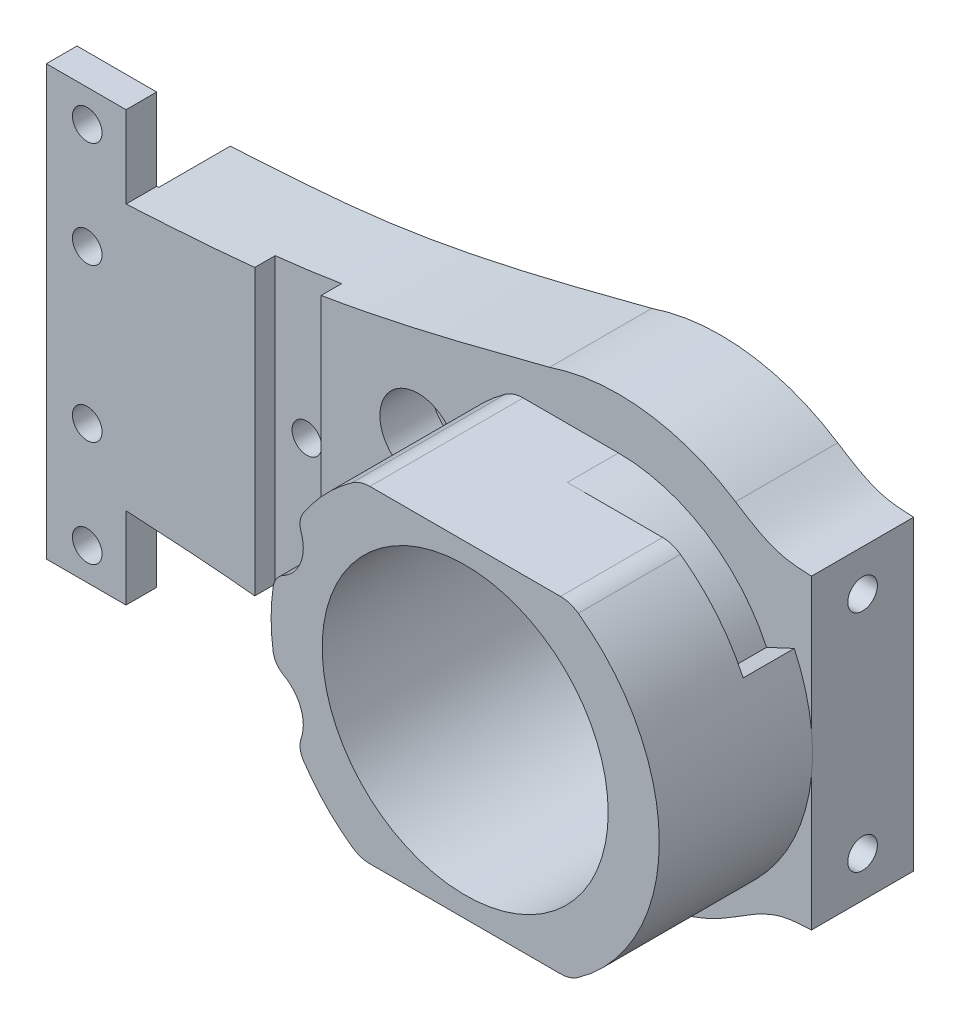
SolidWorks part; units mm, degrees
ref_plane "Front Plane" through (0, 0, 0) normal (0, 0, 1) x (1, 0, 0)
ref_plane "Top Plane" through (0, 0, 0) normal (0, 1, 0) x (1, 0, 0)
ref_plane "Right Plane" through (0, 0, 0) normal (1, 0, 0) x (0, 0, -1)
sketch "Sketch1" plane through (0, 0, 0) normal (0, 0, 1) x (1, 0, 0)
  line L0 (-30, 21) -> (-22.2, 21)
  line L1 (44.9, 15) -> (44.9, -15)
  line L2 (-22.2, 21) -> (-22.2, 13)
  line L3 (-30, -21) -> (-30, 21)
  line L4 (-30, 0) -> (0, 0) construction
  line L5 (0, 0) -> (44.9, 0) construction
  line L6 (-30, -21) -> (-22.2, -21)
  line L7 (-22.2, -21) -> (-22.2, -13)
  circle A0 centre (26, 0) radius 14
  arc A1 (19.2579, -19.8883) -> (37.4703, -17.5907) centre (26, 0) ccw
  arc A2 (37.4703, 17.5907) -> (19.2579, 19.8883) centre (26, 0) ccw
  spline S0 degree 3 poles (-22.2, 13) (-17.0873, 13.2934) (-3.0476, 14.0991) (10.5879, 17.6381) (19.2579, 19.8883) knots 0 0 0 0 0.364161 1 1 1 1
  spline S1 degree 3 poles (-22.2, -13) (-17.0873, -13.2934) (-3.0476, -14.0991) (10.5879, -17.6381) (19.2579, -19.8883) knots 0 0 0 0 0.364161 1 1 1 1
  spline S2 degree 3 poles (44.9, 15) (43.9598, 15.0415) (41.2679, 15.1604) (38.9674, 16.6326) (37.4703, 17.5907) knots 0 0 0 0 0.349252 1 1 1 1
  spline S3 degree 3 poles (44.9, -15) (43.9598, -15.0415) (41.2679, -15.1604) (38.9674, -16.6326) (37.4703, -17.5907) knots 0 0 0 0 0.349252 1 1 1 1
  dimension "D4" = 28
  dimension "D5" = 42
  dimension "D1" = 74.9
  dimension "D2" = 42
  dimension "D3" = 30
  dimension "D6" = 56
  dimension "D7" = 30
  dimension "D8" = 7.8
  dimension "D9" = 8
extrude "Extrude1" add sketch "Sketch1" along normal blind 10
sketch "Sketch3" plane through (0, 0, 10) normal (0, 0, 1) x (1, 0, 0)
  circle A0 centre (26, 0) radius 19
  circle A1 centre (26, 0) radius 14
  dimension "D1" = 38
extrude "Extrude2" add sketch "Sketch3" along normal blind 15
sketch "Sketch4" plane through (0, 0, 0) normal (0, 0, -1) x (-1, 0, 0)
  line L0 (30, 21) -> (30, -21) construction
  line L1 (30, 23.4126) -> (22, 23.4126)
  line L2 (30, 23.4126) -> (30, -25.9867)
  line L3 (30, -25.9867) -> (22, -25.9867)
  line L4 (22, 23.4126) -> (22, -25.9867)
  dimension "D1" = 8
extrude "Extrude3" cut sketch "Sketch4" against normal blind 7
hole_wizard "CBORE for M3 Pan Head Machine Screw1" positions "3DSketch1" profile "Sketch5" counterbore size "M3" standard "Ansi Metric" end condition through all
sketch3d "3DSketch1"
  line L0 (6.4, 7.5, 10) -> (6.4, -7.5, 10) construction
  line L3 (6.4, 0, 10) -> (0, 0, 10) construction
  line L4 (-30, 21, 10) -> (-30, -21, 10) construction
  point P0 (6.4, 7.5, 10)
  point P2 (6.4, -7.5, 10)
  dimension "D1" = 7.5
  dimension "D2" = 7.5
  dimension "D3" = 36.4
sketch "Sketch5" plane through (6.4, 7.5, 10) normal (1, 0, 0) x (0, -1, 0)
  line L0 (0, 0) -> (0, 10)
  line L1 (0, 10) -> (1.8, 10)
  line L3 (1.8, 10) -> (1.8, 5)
  line L4 (1.8, 5) -> (3.75, 5)
  line L5 (3.75, 5) -> (3.75, 0)
  line L7 (3.75, 0) -> (0, 0)
  line L11 (0, -6.35) -> (0, 107.95) construction
  dimension "Thru Hole Dia." = 3.6
  dimension "Thru Hole Depth" = 10
  dimension "C'Bore Dia." = 7.5
  dimension "C'Bore Depth" = 5
sketch "Sketch6" plane through (0, 0, 10) normal (0, 0, 1) x (1, 0, 0)
  circle A0 centre (6.4, 7.5) radius 3.75
  circle A1 centre (6.4, -7.5) radius 3.75
  circle A2 centre (6.4, 7.5) radius 3.75 construction
extrude "Extrude4" cut sketch "Sketch6" along normal blind 20
fillet "Fillet1" radius 2 4 edges at (9.5582, -9.5219, 17.5) (7.4017, -3.8863, 17.5) (7.4017, 3.8863, 17.5) (9.5582, 9.5219, 17.5)
sketch "Sketch8" plane through (0, 0, 25) normal (0, 0, 1) x (1, 0, 0)
  line L0 (0, 0) -> (9, 0) construction
  line L1 (15.753, 16) -> (36.247, 16)
  line L2 (15.753, 16) -> (15.753, 23.4488)
  line L3 (15.753, 23.4488) -> (36.247, 23.4488)
  line L4 (36.247, 16) -> (36.247, 23.4488)
  line L5 (26, 0) -> (26, 26.3314) construction
  line L6 (15.753, -23.4488) -> (36.247, -23.4488)
  line L7 (36.247, -16) -> (36.247, -23.4488)
  line L8 (15.753, -16) -> (36.247, -16)
  line L9 (15.753, -16) -> (15.753, -23.4488)
  circle A0 centre (26, 0) radius 19 construction
  point P13 (26, 16)
  dimension "D1" = 16
extrude "Extrude5" cut sketch "Sketch8" against normal up to surface (15 mm away) up to face at (9.4784, 0.1953, 10)
fillet "Fillet2" radius 3 4 edges at (15.753, -16, 17.5) (36.247, -16, 17.5) (36.247, 16, 17.5) (15.753, 16, 17.5)
sketch "Sketch11" plane through (0, 0, 10) normal (0, 0, 1) x (1, 0, 0)
  line L0 (16.6726, 16) -> (35.3274, 16) construction
  line L1 (26, 16) -> (26, 19)
  line L2 (40.4989, 6.7663) -> (43.2174, 8.0349)
  line L3 (26, -16) -> (26, -19)
  line L5 (40.4989, 6.7663) -> (8.7826, -8.0349) construction
  line L6 (8.7826, -8.0349) -> (11.5011, -6.7663)
  arc A0 (11.5011, -6.7663) -> (26, -16) centre (26, 0) ccw
  arc A1 (8.7826, -8.0349) -> (26, -19) centre (26, 0) ccw
  arc A2 (40.4989, 6.7663) -> (26, 16) centre (26, 0) ccw
  arc A3 (43.2174, 8.0349) -> (26, 19) centre (26, 0) ccw
extrude "Extrude8" cut sketch "Sketch11" along normal blind 5
hole_wizard "Ø2.9 (2.9) Diameter Hole1" positions "3DSketch2" profile "Sketch13" hole size "Ø2.9" standard "Ansi Metric"
sketch3d "3DSketch2"
  line L0 (-26, -21, 10) -> (-26, 21, 10) construction
  line L1 (-30, -21, 10) -> (-22.2, -21, 10) construction
  line L2 (-22.2, 21, 10) -> (-30, 21, 10) construction
  line L6 (-30, 21, 10) -> (-30, -21, 10) construction
  point P0 (-26, -17.85, 10)
  point P2 (-26, -7.5, 10)
  point P4 (-26, 7.5, 10)
  point P6 (-26, 17.85, 10)
  point P22 (-26, 0, 10)
  dimension "D1" = 15
  dimension "D2" = 7.5
  dimension "D3" = 3.15
  dimension "D4" = 3.15
  dimension "D5" = 4
sketch "Sketch13" plane through (-26, -17.85, 10) normal (1, 0, 0) x (0, -1, 0)
  line L0 (0, 0) -> (0, 10)
  line L1 (0, 10) -> (1.45, 10)
  line L2 (1.45, 10) -> (1.45, 0)
  line L5 (1.45, 0) -> (0, 0)
  line L10 (0, 10) -> (-1.45, 10) construction
  line L11 (0, -6.35) -> (0, 107.95) construction
  dimension "Hole Dia." = 2.9
  dimension "Hole Depth" = 10
  dimension "Drill Angle" = 180
sketch "Sketch14" plane through (0, 0, 10) normal (0, 0, 1) x (1, 0, 0)
  line L0 (-30, 21) -> (-30, -21) construction
  line L1 (-3.1, -23.334) -> (-9.6, -23.334)
  line L2 (-3.1, -23.334) -> (-3.1, 21.2199)
  line L3 (-3.1, 21.2199) -> (-9.6, 21.2199)
  line L4 (-9.6, -23.334) -> (-9.6, 21.2199)
  dimension "D1" = 6.5
  dimension "D2" = 20.4
extrude "Extrude9" cut sketch "Sketch14" against normal blind 2
sketch "Sketch15" plane through (0, 0, 8) normal (0, 0, 1) x (1, 0, 0)
  line L0 (-6.5, -14.2974) -> (-6.5, 14.2974) construction
  line L1 (-9.6, 13.9272) -> (-9.6, -13.9272) construction
  circle A0 centre (-6.5, 0) radius 1.45
  spline S0 degree 3 poles (-9.6, -13.9272) (-8.7037, -14.0224) (-6.5313, -14.276) (-4.3688, -14.5963) (-3.1, -14.8043) knots 0.299863 0.299863 0.299863 0.299863 0.364161 0.455943 0.455943 0.455943 0.455943 construction
  spline S1 degree 3 poles (-3.1, 14.8043) (-4.3688, 14.5963) (-6.5313, 14.276) (-8.7037, 14.0224) (-9.6, 13.9272) knots 0.544057 0.544057 0.544057 0.544057 0.635839 0.700137 0.700137 0.700137 0.700137 construction
  point P8 (-6.5, 0)
  dimension "D1" = 2.9
  dimension "D2" = 3.1
extrude "Extrude10" cut sketch "Sketch15" against normal blind 10
sketch "Sketch16" plane through (44.9, 0, 0) normal (1, 0, 0) x (0, 0, -1)
  line L0 (-5, -15) -> (-5, 15) construction
  line L2 (-10, 15) -> (0, 15) construction
  line L3 (-10, -15) -> (-10, -1.9468) construction
  circle A0 centre (-5, -11) radius 1.45
  circle A1 centre (-5, 11) radius 1.45
  dimension "D1" = 2.9
  dimension "D2" = 4
  dimension "D3" = 4
  dimension "D4" = 5
extrude "Extrude11" cut sketch "Sketch16" against normal blind 6
